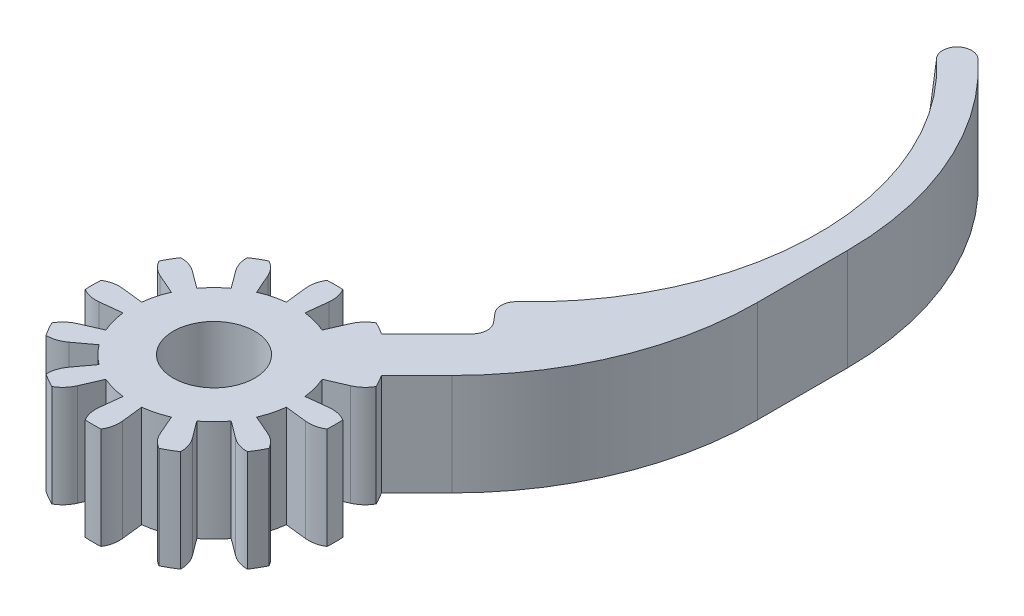
SolidWorks part; units mm, degrees
ref_plane "Plan de face" through (0, 0, 0) normal (0, 0, 1) x (1, 0, 0)
ref_plane "Plan de dessus" through (0, 0, 0) normal (0, 1, 0) x (1, 0, 0)
ref_plane "Plan de droite" through (0, 0, 0) normal (1, 0, 0) x (0, 0, -1)
sketch "Esquisse1" plane through (0, 0, 0) normal (0, 1, 0) x (1, 0, 0)
  line L0 (-18.0504, 0) -> (30.2368, 0) construction
  line L1 (0, 16.9051) -> (0, -14.3396) construction
  line L2 (0, 0) -> (-4.5652, 17.0374) construction
  line L51 (0, 0) -> (35.8316, 35.8316) construction
  line L52 (0, 0) -> (-1.8459, 16.2017) construction
  line L53 (-8.75, 40) -> (13.8918, 66.9834) construction
  line L54 (-8.75, 40) -> (13.2955, 13.7272) construction
  line L55 (-8.75, 40) -> (38.0168, 40) construction
  line L56 (10.1877, 62.5691) -> (7.9625, 59.9172)
  line L57 (10.9958, 16.4678) -> (7.9625, 20.0828)
  line L58 (22.25, 40) -> (22.25, -33.4016) construction
  line L59 (9.9946, 6.459) -> (13.4632, 9.9277)
  line L60 (6.459, 9.9946) -> (10.9074, 14.443)
  line L61 (17.25, 31.7709) -> (17.25, -36.5745) construction
  line L62 (22.25, 40) -> (22.25, 31.1409)
  line L65 (0, 0) -> (-1.1064, 16.8807) construction
  line L66 (-1.1547, 10.1344) -> (-0.9141, 8.0231)
  line L67 (1.1547, 10.1344) -> (0.9141, 8.0231)
  line L68 (4.0672, 9.354) -> (3.2199, 7.4053)
  line L70 (-8.75, 40) -> (-8.75, 0) construction
  line L72 (9.354, 4.0672) -> (7.4053, 3.2199)
  line L73 (10.1344, 1.1547) -> (8.0231, 0.9141)
  line L74 (10.1344, -1.1547) -> (8.0231, -0.9141)
  line L75 (9.354, -4.0672) -> (7.4053, -3.2199)
  line L76 (8.1993, -6.0672) -> (6.4911, -4.8032)
  line L77 (6.0672, -8.1993) -> (4.8032, -6.4911)
  line L78 (4.0672, -9.354) -> (3.2199, -7.4053)
  line L79 (1.1547, -10.1344) -> (0.9141, -8.0231)
  line L80 (-1.1547, -10.1344) -> (-0.9141, -8.0231)
  line L81 (-4.0672, -9.354) -> (-3.2199, -7.4053)
  line L82 (-6.0672, -8.1993) -> (-4.8032, -6.4911)
  line L83 (-8.1993, -6.0672) -> (-6.4911, -4.8032)
  line L84 (-9.354, -4.0672) -> (-7.4053, -3.2199)
  line L85 (-10.1344, -1.1547) -> (-8.0231, -0.9141)
  line L86 (-10.1344, 1.1547) -> (-8.0231, 0.9141)
  line L87 (-9.354, 4.0672) -> (-7.4053, 3.2199)
  line L88 (-8.1993, 6.0672) -> (-6.4911, 4.8032)
  line L89 (-6.0672, 8.1993) -> (-4.8032, 6.4911)
  line L90 (-4.0672, 9.354) -> (-3.2199, 7.4053)
  line L91 (6.0672, 8.1993) -> (4.8032, 6.4911)
  line L92 (8.1993, 6.0672) -> (6.4911, 4.8032)
  circle A0 centre (0, 0) radius 11.9 construction
  circle A26 centre (-8.75, 40) radius 25
  circle A27 centre (0, 0) radius 4
  arc A28 (7.9625, 59.9172) -> (7.9625, 20.0828) centre (-8.75, 40) cw
  arc A29 (12.3581, 62.7035) -> (22.25, 40) centre (-8.75, 40) cw
  circle A31 centre (0, 0) radius 8.075 construction
  circle A32 centre (0, 0) radius 10.2 construction
  arc A33 (-1.1547, 10.1344) -> (-0.7783, 11.8745) centre (1.6032, 10.4487) cw
  arc A34 (-0.9141, 8.0231) -> (-2.09, 7.7999) centre (0, 0) ccw
  arc A35 (0.7783, 11.8745) -> (-0.7783, 11.8745) centre (0, 0) ccw
  arc A36 (0.9141, 8.0231) -> (2.09, 7.7999) centre (0, 0) cw
  arc A37 (1.1547, 10.1344) -> (0.7783, 11.8745) centre (-1.6032, 10.4487) ccw
  arc A38 (3.2199, 7.4053) -> (2.09, 7.7999) centre (0, 0) ccw
  arc A39 (4.0672, 9.354) -> (5.2632, 10.6728) centre (6.6128, 8.2472) cw
  arc A40 (10.9074, 14.443) -> (10.9958, 16.4678) centre (9.8468, 15.5036) ccw
  arc A41 (5.2632, 10.6728) -> (6.459, 9.9946) centre (0, 0) cw
  arc A42 (9.9946, 6.459) -> (10.6728, 5.2632) centre (0, 0) cw
  arc A43 (13.4632, 9.9277) -> (22.25, 31.1409) centre (-7.75, 31.1409) ccw
  arc A46 (9.354, 4.0672) -> (10.6728, 5.2632) centre (8.2472, 6.6128) ccw
  arc A47 (7.4053, 3.2199) -> (7.7999, 2.09) centre (0, 0) cw
  arc A48 (8.0231, 0.9141) -> (7.7999, 2.09) centre (0, 0) ccw
  arc A49 (10.1344, 1.1547) -> (11.8745, 0.7783) centre (10.4487, -1.6032) cw
  arc A50 (11.8745, -0.7783) -> (11.8745, 0.7783) centre (0, 0) ccw
  arc A51 (10.1344, -1.1547) -> (11.8745, -0.7783) centre (10.4487, 1.6032) ccw
  arc A52 (8.0231, -0.9141) -> (7.7999, -2.09) centre (0, 0) cw
  arc A53 (7.4053, -3.2199) -> (7.7999, -2.09) centre (0, 0) ccw
  arc A54 (9.354, -4.0672) -> (10.6728, -5.2632) centre (8.2472, -6.6128) cw
  arc A55 (9.8945, -6.6113) -> (10.6728, -5.2632) centre (0, 0) ccw
  arc A56 (8.1993, -6.0672) -> (9.8945, -6.6113) centre (9.8504, -3.8359) ccw
  arc A57 (6.4911, -4.8032) -> (5.7099, -5.7099) centre (0, 0) cw
  arc A58 (4.8032, -6.4911) -> (5.7099, -5.7099) centre (0, 0) ccw
  arc A59 (6.0672, -8.1993) -> (6.6113, -9.8945) centre (3.8359, -9.8504) cw
  arc A60 (5.2632, -10.6728) -> (6.6113, -9.8945) centre (0, 0) ccw
  arc A61 (4.0672, -9.354) -> (5.2632, -10.6728) centre (6.6128, -8.2472) ccw
  arc A62 (3.2199, -7.4053) -> (2.09, -7.7999) centre (0, 0) cw
  arc A63 (0.9141, -8.0231) -> (2.09, -7.7999) centre (0, 0) ccw
  arc A64 (1.1547, -10.1344) -> (0.7783, -11.8745) centre (-1.6032, -10.4487) cw
  arc A65 (-0.7783, -11.8745) -> (0.7783, -11.8745) centre (0, 0) ccw
  arc A66 (-1.1547, -10.1344) -> (-0.7783, -11.8745) centre (1.6032, -10.4487) ccw
  arc A67 (-0.9141, -8.0231) -> (-2.09, -7.7999) centre (0, 0) cw
  arc A68 (-3.2199, -7.4053) -> (-2.09, -7.7999) centre (0, 0) ccw
  arc A69 (-4.0672, -9.354) -> (-5.2632, -10.6728) centre (-6.6128, -8.2472) cw
  arc A70 (-6.6113, -9.8945) -> (-5.2632, -10.6728) centre (0, 0) ccw
  arc A71 (-6.0672, -8.1993) -> (-6.6113, -9.8945) centre (-3.8359, -9.8504) ccw
  arc A72 (-4.8032, -6.4911) -> (-5.7099, -5.7099) centre (0, 0) cw
  arc A73 (-6.4911, -4.8032) -> (-5.7099, -5.7099) centre (0, 0) ccw
  arc A74 (-8.1993, -6.0672) -> (-9.8945, -6.6113) centre (-9.8504, -3.8359) cw
  arc A75 (-10.6728, -5.2632) -> (-9.8945, -6.6113) centre (0, 0) ccw
  arc A76 (-9.354, -4.0672) -> (-10.6728, -5.2632) centre (-8.2472, -6.6128) ccw
  arc A77 (-7.4053, -3.2199) -> (-7.7999, -2.09) centre (0, 0) cw
  arc A78 (-8.0231, -0.9141) -> (-7.7999, -2.09) centre (0, 0) ccw
  arc A79 (-10.1344, -1.1547) -> (-11.8745, -0.7783) centre (-10.4487, 1.6032) cw
  arc A80 (-11.8745, 0.7783) -> (-11.8745, -0.7783) centre (0, 0) ccw
  arc A81 (-10.1344, 1.1547) -> (-11.8745, 0.7783) centre (-10.4487, -1.6032) ccw
  arc A82 (-8.0231, 0.9141) -> (-7.7999, 2.09) centre (0, 0) cw
  arc A83 (-7.4053, 3.2199) -> (-7.7999, 2.09) centre (0, 0) ccw
  arc A84 (-9.354, 4.0672) -> (-10.6728, 5.2632) centre (-8.2472, 6.6128) cw
  arc A85 (-9.8945, 6.6113) -> (-10.6728, 5.2632) centre (0, 0) ccw
  arc A86 (-8.1993, 6.0672) -> (-9.8945, 6.6113) centre (-9.8504, 3.8359) ccw
  arc A87 (-6.4911, 4.8032) -> (-5.7099, 5.7099) centre (0, 0) cw
  arc A88 (-4.8032, 6.4911) -> (-5.7099, 5.7099) centre (0, 0) ccw
  arc A89 (-6.0672, 8.1993) -> (-6.6113, 9.8945) centre (-3.8359, 9.8504) cw
  arc A90 (-5.2632, 10.6728) -> (-6.6113, 9.8945) centre (0, 0) ccw
  arc A91 (-4.0672, 9.354) -> (-5.2632, 10.6728) centre (-6.6128, 8.2472) ccw
  arc A92 (-3.2199, 7.4053) -> (-2.09, 7.7999) centre (0, 0) cw
  arc A93 (6.0672, 8.1993) -> (6.6113, 9.8945) centre (3.8359, 9.8504) ccw
  arc A94 (4.8032, 6.4911) -> (5.7099, 5.7099) centre (0, 0) cw
  arc A95 (6.4911, 4.8032) -> (5.7099, 5.7099) centre (0, 0) ccw
  arc A96 (8.1993, 6.0672) -> (9.8945, 6.6113) centre (9.8504, 3.8359) cw
  arc A99 (12.3581, 62.7035) -> (10.1877, 62.5691) centre (11.3368, 61.6049) ccw
  arc A100 (6.6113, 9.8945) -> (5.2632, 10.6728) centre (0, 0) ccw
  arc A101 (10.6728, 5.2632) -> (9.8945, 6.6113) centre (0, 0) ccw
  point P14 (0, 11.9)
  point P37 (22.25, 18.7145)
  point P46 (17.25, 20.2855)
  point P52 (10.855, 16.6356)
  point P65 (17.25, 23.2668)
  point P90 (11.1764, 63.7474)
  point P133 (0, 0)
  point P170 (0, 0)
  dimension "D2" = 20.4
  dimension "D4" = 23.8
  dimension "D6" = 6.5
  dimension "D8" = 40
  dimension "D9" = 50
  dimension "D10" = 8
  dimension "D11" = 5
  dimension "D12" = 26
  dimension "D15" = 45
  dimension "D5" = 16.15
  dimension "D18" = 12
  dimension "D19" = 8.75
  dimension "D20" = 30
  dimension "D21" = 1.5
  dimension "D3" = 15
  dimension "D7" = 3.75
  dimension "D13" = 50
  dimension "D14" = 50
  dimension "D16" = 5
  dimension "D17" = 5
extrude "Boss.-Extru.1" add sketch "Esquisse1" along normal blind 10 contours A92 L90 A91 A90 A89 L89 A88 A87 L88 A86 A85 A84 L87 A83 A82 L86 A81 A80 A79 L85 A78 A77 L84 A76 A75 A74 L83 A73 A72 L82 A71 A70 A69 L81 A68 A67 L80 A66 A65 A64 L79 A63 A62 L78 A61 A60 A59 L77 A58 A57 L76
chamfer "Chanfrein1" distance 20 angle 6.03 1 edges at (17.25, 10, -40)
fillet "Congé1" radius 1.5 2 edges at (8.981, 5, -18.869) (8.981, 5, -61.131)
